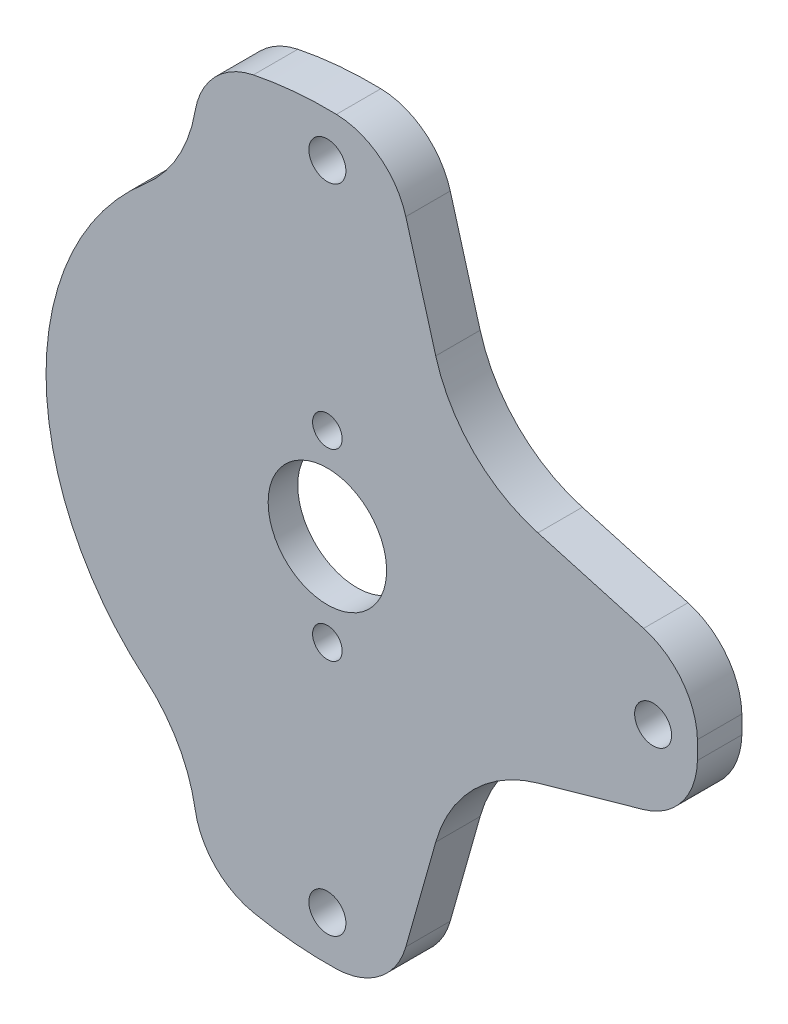
SolidWorks part; units mm, degrees
ref_plane "前视基准面" through (0, 0, 0) normal (0, 0, 1) x (1, 0, 0)
ref_plane "上视基准面" through (0, 0, 0) normal (0, 1, 0) x (1, 0, 0)
ref_plane "右视基准面" through (0, 0, 0) normal (1, 0, 0) x (0, 0, -1)
other "Configuration Table"
sketch "草图1" plane through (0, 0, 0) normal (0, 0, 1) x (1, 0, 0)
  line L0 (0, 0) -> (0, 22) construction
  line L1 (0, 0) -> (22, 0) construction
  circle A0 centre (0, 0) radius 22 construction
  circle A1 centre (0, 0) radius 19 construction
  circle A2 centre (0, 0) radius 25
  circle A3 centre (0, 22) radius 1.25
  circle A4 centre (22, 0) radius 1.25
  circle A5 centre (0, -22) radius 1.25
  dimension "D1" = 44
  dimension "D2" = 38
  dimension "D3" = 3
  dimension "D4" = 2.5
  dimension "D6" = 90
  dimension "D5" = 3
extrude "凸台-拉伸1" add sketch "草图1" along normal blind 3
sketch "草图3" plane through (0, 0, 0) normal (0, 0, -1) x (-1, 0, 0)
  line L0 (0, 0) -> (0, 22) construction
  circle A0 centre (0, 0) radius 10.5
  circle A1 centre (0, 0) radius 4
  circle A2 centre (0, 6.2) radius 1
  circle A3 centre (0, -6.2) radius 1
  dimension "D1" = 21
  dimension "D2" = 8
  dimension "D3" = 2
  dimension "D4" = 2
  dimension "D5" = 6.2
  dimension "D6" = 6.2
extrude "切除-拉伸1" cut sketch "草图3" against normal blind 1
extrude "切除-拉伸2" cut sketch "草图3<2>" against normal through all both and the other way through all contours A2 | A1 | A3 region at (0, 0, 0) region at (0, 6.2, 0) region at (0, -6.2, 0)
sketch "草图3<2>" plane through (0, 0, 0) normal (0, 0, -1) x (-1, 0, 0) same geometry as "草图3"
sketch "草图4" plane through (0, 0, 0) normal (0, 0, -1) x (-1, 0, 0)
  line L0 (0, 0) -> (0, 22) construction
  line L1 (0, 0) -> (-22, 0) construction
  circle A0 centre (0, 22) radius 2.5
  circle A1 centre (-22, 0) radius 2.5
  circle A2 centre (0, -22) radius 2.5
  point P3 (-10.8559, -10.2374)
  point P4 (0, 0)
  dimension "D1" = 5
  dimension "D3" = 90
  dimension "D2" = 3
sketch "草图5" plane through (0, 0, 0) normal (0, 0, -1) x (-1, 0, 0)
  line L0 (0, 0) -> (-17.6777, 17.6777) construction
  line L1 (0, 0) -> (-22, 0) construction
  line L2 (-24.6137, 4.3776) -> (-8.8388, 8.8388)
  line L3 (-4.3776, 24.6137) -> (-8.8388, 8.8388)
  line L4 (-4.3776, -24.6137) -> (-8.8388, -8.8388)
  line L5 (-24.6137, -4.3776) -> (-8.8388, -8.8388)
  line L6 (0, 0) -> (-8.8388, 8.8388) construction
  line L7 (0, 0) -> (-8.8388, -8.8388) construction
  line L8 (0, 0) -> (0, 22) construction
  line L9 (9, -16.7332) -> (9, -23.3238)
  line L10 (9, 23.3238) -> (9, 16.7332)
  circle A0 centre (0, 0) radius 25 construction
  arc A1 (-4.3776, 24.6137) -> (-24.6137, 4.3776) centre (0, 0) ccw
  arc A2 (-24.6137, -4.3776) -> (-4.3776, -24.6137) centre (0, 0) ccw
  arc A3 (9, -23.3238) -> (9, 23.3238) centre (0, 0) ccw
  arc A4 (9, -16.7332) -> (9, 16.7332) centre (0, 0) ccw
  circle A5 centre (0, 0) radius 19 construction
  dimension "D1" = 15
  dimension "45" = 45
  dimension "D2" = 15
  dimension "D4" = 90
  dimension "D5" = 9
  dimension "D3" = 2
extrude "切除-拉伸5" cut sketch "草图5" against normal blind 10
fillet "圆角2" radius 5 6 edges at (4.3776, 24.6137, 1.5) (4.3776, -24.6137, 1.5) (24.6137, -4.3776, 1.5) (24.6137, 4.3776, 1.5) (-9, 23.3238, 1.5) (-9, -23.3238, 1.5)
fillet "圆角3" radius 10 4 edges at (8.8388, 8.8388, 1.5) (8.8388, -8.8388, 1.5) (-9, -16.7332, 1.5) (-9, 16.7332, 1.5)
